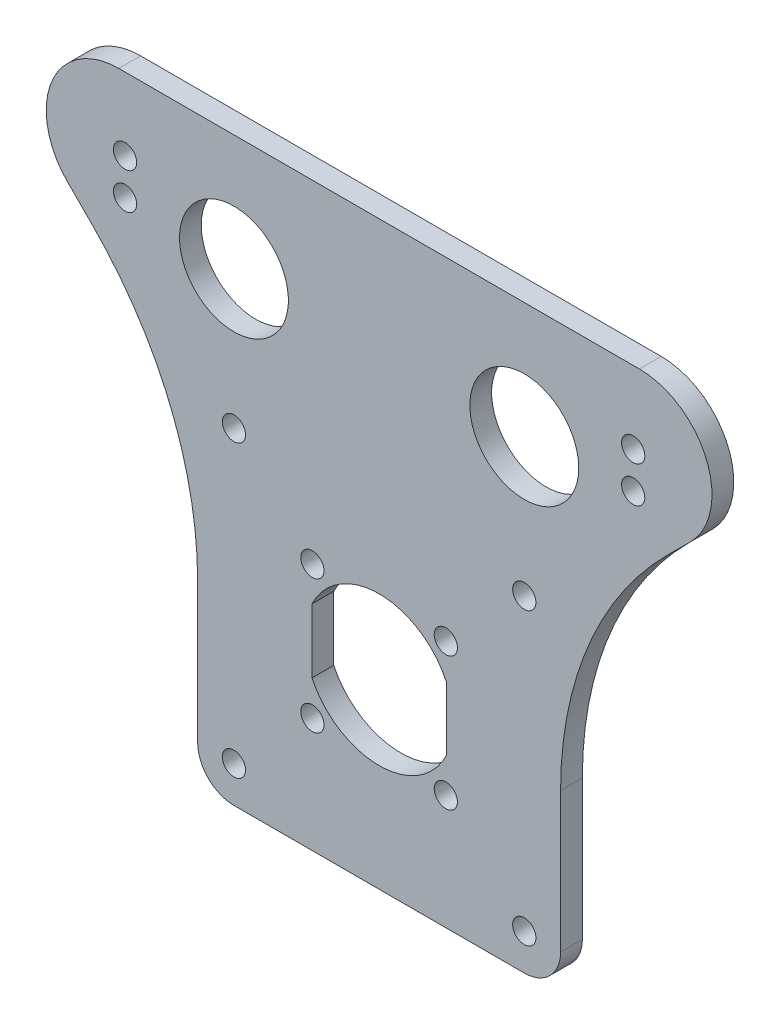
SolidWorks part; units mm, degrees
ref_plane "正面" through (0, 0, 0) normal (0, 0, 1) x (1, 0, 0)
ref_plane "平面" through (0, 0, 0) normal (0, 1, 0) x (1, 0, 0)
ref_plane "右側面" through (0, 0, 0) normal (1, 0, 0) x (0, 0, -1)
sketch "ｽｹｯﾁ1" plane through (0, 0, 0) normal (0, 0, 1) x (1, 0, 0)
  line L1 (-20, 20) -> (20, 20) construction
  line L2 (-20, 20) -> (-20, -20) construction
  line L3 (-20, -20) -> (20, -20) construction
  line L4 (20, 20) -> (20, -20) construction
  line L5 (-20, 20) -> (20, -20) construction
  line L6 (-20, -20) -> (20, 20) construction
  line L7 (-9.1924, 9.1924) -> (9.1924, 9.1924) construction
  line L8 (-9.1924, 9.1924) -> (-9.1924, -9.1924) construction
  line L9 (-9.1924, -9.1924) -> (9.1924, -9.1924) construction
  line L10 (9.1924, 9.1924) -> (9.1924, -9.1924) construction
  line L11 (-9.1924, 9.1924) -> (9.1924, -9.1924) construction
  line L12 (-9.1924, -9.1924) -> (9.1924, 9.1924) construction
  line L13 (-25, 25) -> (25, 25)
  line L14 (-25, 25) -> (-25, -25)
  line L15 (-25, -25) -> (25, -25)
  line L16 (25, 25) -> (25, -25)
  line L17 (-25, 25) -> (25, -25) construction
  line L18 (-25, -25) -> (25, 25) construction
  circle A0 centre (-20, 20) radius 1.6
  circle A1 centre (-9.1924, 9.1924) radius 1.6
  circle A2 centre (9.1924, 9.1924) radius 1.6
  circle A3 centre (20, 20) radius 1.6
  circle A4 centre (9.1924, -9.1924) radius 1.6
  circle A5 centre (20, -20) radius 1.6
  circle A6 centre (-9.1924, -9.1924) radius 1.6
  circle A7 centre (-20, -20) radius 1.6
  point P0 (0, 0)
  point P5 (0, 0)
  point P10 (0, 0)
  dimension "D3" = 4
  dimension "D4" = 3.2
  dimension "D1" = 40
  dimension "D2" = 13
  dimension "D5" = 50
extrude "ﾎﾞｽ - 押し出し1" add sketch "ｽｹｯﾁ1" along normal blind 3
fillet "ﾌｨﾚｯﾄ1" radius 5 4 edges at (25, -25, 1.5) (-25, -25, 1.5) (-25, 25, 1.5) (25, 25, 1.5)
sketch "ｽｹｯﾁ2" plane through (0, 0, 3) normal (0, 0, 1) x (1, 0, 0)
  line L0 (-9.25, 4.4159) -> (-9.25, -4.4159)
  line L2 (9.25, -4.4159) -> (9.25, 4.4159)
  arc A0 (-9.25, -4.4159) -> (9.25, -4.4159) centre (0, 0) ccw
  arc A1 (9.25, 4.4159) -> (-9.25, 4.4159) centre (0, 0) ccw
  dimension "D1" = 18.5
  dimension "D2" = 20.5
extrude "ｶｯﾄ - 押し出し1" cut sketch "ｽｹｯﾁ2" against normal through all
sketch "ｽｹｯﾁ3" plane through (0, 0, 3) normal (0, 0, 1) x (1, 0, 0)
  line L0 (-25, 20) -> (-42.9289, 37.9289)
  line L1 (-35.8579, 55) -> (35.8579, 55)
  line L2 (42.9289, 37.9289) -> (25, 20)
  line L3 (25, -20) -> (25, 20) construction
  line L4 (-25, 20) -> (-25, -20) construction
  line L5 (20, 25) -> (-20, 25) construction
  line L10 (-20, -25) -> (20, -25)
  line L11 (25, -20) -> (25, 20)
  line L12 (20, 25) -> (-20, 25)
  line L13 (-25, 20) -> (-25, -20)
  line L16 (20, 25) -> (-20, 25)
  arc A0 (35.8579, 55) -> (42.9289, 37.9289) centre (35.8579, 45) cw
  arc A1 (-42.9289, 37.9289) -> (-35.8579, 55) centre (-35.8579, 45) cw
  arc A6 (20, -25) -> (25, -20) centre (20, -20) ccw
  arc A7 (25, 20) -> (20, 25) centre (20, 20) ccw
  arc A8 (-20, 25) -> (-25, 20) centre (-20, 20) ccw
  arc A9 (-25, -20) -> (-20, -25) centre (-20, -20) ccw
  arc A11 (25, 20) -> (20, 25) centre (20, 20) ccw
  arc A12 (-20, 25) -> (-25, 20) centre (-20, 20) ccw
  dimension "D4" = 10
  dimension "D1" = 135
  dimension "D2" = 135
  dimension "D3" = 30
  dimension "D5" = 0
extrude "ﾎﾞｽ - 押し出し2" add sketch "ｽｹｯﾁ3" against normal through all
fillet "ﾌｨﾚｯﾄ2" radius 50 2 edges at (-25, 20, 1.5) (25, 20, 1.5)
sketch "ｽｹｯﾁ4" plane through (0, 0, 3) normal (0, 0, 1) x (1, 0, 0)
  line L0 (-50, 45) -> (50, 45) construction
  line L1 (-42.9289, 37.9289) -> (-39.6447, 34.6447) construction
  line L2 (39.6447, 34.6447) -> (42.9289, 37.9289) construction
  line L3 (35.8579, 55) -> (-35.8579, 55) construction
  line L4 (0, 0) -> (0, 45) construction
  circle A0 centre (-35, 45) radius 1.6
  circle A1 centre (35, 45) radius 1.6
  dimension "D2" = 35
  dimension "D3" = 3.2
  dimension "D1" = 10
extrude "ｶｯﾄ - 押し出し2" cut sketch "ｽｹｯﾁ4" against normal through all
sketch "ｽｹｯﾁ5" plane through (0, 0, 3) normal (0, 0, 1) x (1, 0, 0)
  line L0 (0, 0) -> (0, 55) construction
  line L1 (35.8579, 55) -> (-35.8579, 55) construction
  circle A0 centre (20, 39) radius 7.5
  circle A1 centre (-20, 39) radius 7.5
  dimension "D1" = 15
  dimension "D2" = 16
  dimension "D3" = 20
extrude "ｶｯﾄ - 押し出し3" cut sketch "ｽｹｯﾁ5" against normal through all
sketch "ｽｹｯﾁ6" plane through (0, 0, 0) normal (0, 0, -1) x (-1, 0, 0)
  line L0 (-35, 45) -> (-35, 40) construction
  line L1 (0, 0) -> (0, 55) construction
  line L2 (-35.8579, 55) -> (35.8579, 55) construction
  circle A0 centre (-35, 40) radius 1.6
  circle A1 centre (35, 40) radius 1.6
  dimension "D1" = 5
  dimension "D2" = 3.2
extrude "ｶｯﾄ - 押し出し4" cut sketch "ｽｹｯﾁ6" against normal through all
